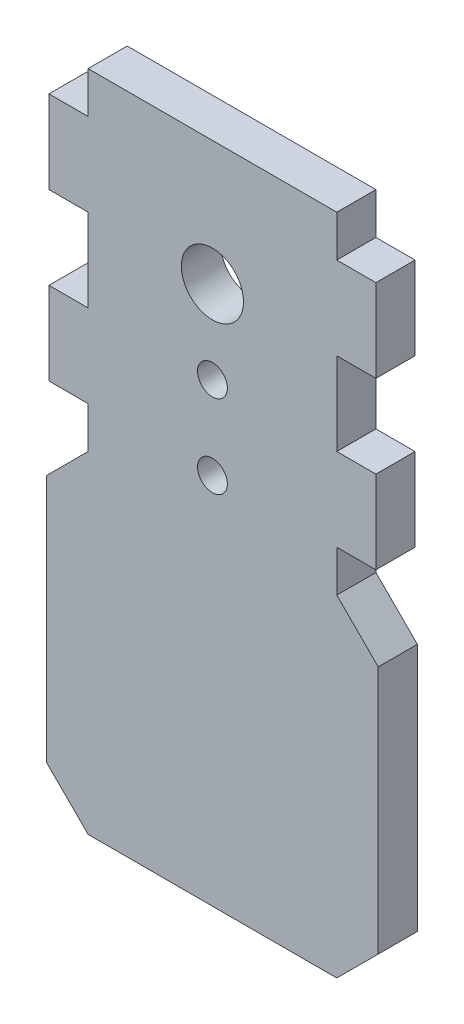
SolidWorks part; units mm, degrees
ref_plane "Front Plane" through (0, 0, 0) normal (0, 0, 1) x (1, 0, 0)
ref_plane "Top Plane" through (0, 0, 0) normal (0, 1, 0) x (1, 0, 0)
ref_plane "Right Plane" through (0, 0, 0) normal (1, 0, 0) x (0, 0, -1)
sketch "Sketch1" plane through (0, 0, 0) normal (0, 0, 1) x (1, 0, 0)
  line L0 (-19.05, 50.8) -> (-19.05, 0) construction
  line L1 (0, 0) -> (-38.1, 0)
  line L2 (0, 0) -> (0, 6.35)
  line L3 (0, 50.8) -> (-38.1, 50.8)
  line L4 (-38.1, 0) -> (-38.1, 6.35)
  line L5 (-38.1, 25.4) -> (0, 25.4) construction
  line L6 (-44.0944, 6.35) -> (-44.0944, 19.05)
  line L7 (-38.1, 44.45) -> (-44.0944, 44.45)
  line L8 (-38.1, 19.05) -> (-38.1, 31.75)
  line L9 (-38.1, 31.75) -> (-44.0944, 31.75)
  line L10 (-44.0944, 44.45) -> (-44.0944, 31.75)
  line L11 (-38.1, 19.05) -> (-44.0944, 19.05)
  line L12 (0, 19.05) -> (0, 31.75)
  line L13 (-38.1, 6.35) -> (-44.0944, 6.35)
  line L14 (0, 6.35) -> (5.9944, 6.35)
  line L15 (0, 44.45) -> (0, 50.8)
  line L16 (0, 19.05) -> (5.9944, 19.05)
  line L17 (5.9944, 44.45) -> (5.9944, 31.75)
  line L18 (0, 31.75) -> (5.9944, 31.75)
  line L20 (0, 44.45) -> (5.9944, 44.45)
  line L21 (5.9944, 6.35) -> (5.9944, 19.05)
  line L22 (-38.1, 44.45) -> (-38.1, 50.8)
  dimension "D1" = 38.1
  dimension "D2" = 50.8
  dimension "D3" = 12.7
  dimension "D4" = 5.9944
  dimension "D5" = 6.35
extrude "Boss-Extrude1" add sketch "Sketch1" along normal blind 5.9944
sketch "Sketch2" plane through (0, 0, 0) normal (0, 0, -1) x (-1, 0, 0)
  line L0 (19.05, 0) -> (19.05, 50.8) construction
  line L1 (38.1, 0) -> (0, 0) construction
  line L2 (0, 50.8) -> (38.1, 50.8) construction
  circle A0 centre (19.05, 31.75) radius 4.7625
  dimension "D1" = 19.05
  dimension "D2" = 9.525
extrude "Cut-Extrude1" cut sketch "Sketch2" against normal through all
sketch "Sketch3" plane through (0, 0, 5.9944) normal (0, 0, 1) x (1, 0, 0)
  circle A0 centre (-19.05, 19.05) radius 2.286
  circle A1 centre (-19.05, 31.75) radius 4.7625 construction
  circle A2 centre (-19.05, 6.35) radius 2.286
  dimension "D1" = 12.7
  dimension "D3" = 4.572
  dimension "D2" = 2
extrude "Cut-Extrude2" cut sketch "Sketch3" against normal through all
sketch "Sketch4" plane through (0, 0, 5.9944) normal (0, 0, 1) x (1, 0, 0)
  line L0 (-19.05, 0) -> (-19.05, -50.8) construction
  line L1 (-38.1, 0) -> (0, 0) construction
  line L3 (6.35, -50.8) -> (-44.45, -50.8)
  line L4 (6.35, -50.8) -> (6.35, 0)
  line L5 (6.35, 0) -> (-44.45, 0)
  line L6 (-44.45, -50.8) -> (-44.45, 0)
  line L7 (6.35, -50.8) -> (-44.45, 0) construction
  line L8 (6.35, 0) -> (-44.45, -50.8) construction
  point P4 (-19.05, -25.4)
  dimension "D1" = 50.8
  dimension "D2" = 50.8
extrude "Boss-Extrude2" add sketch "Sketch4" against normal up to surface (5.9944 mm away) up to face at (-16.764, 6.35, 0)
chamfer "Chamfer1" distance 6.35 angle 45 4 edges at (6.35, 0, 2.9972) (6.35, -50.8, 2.9972) (-44.45, -50.8, 2.9972) (-44.45, 0, 2.9972)
